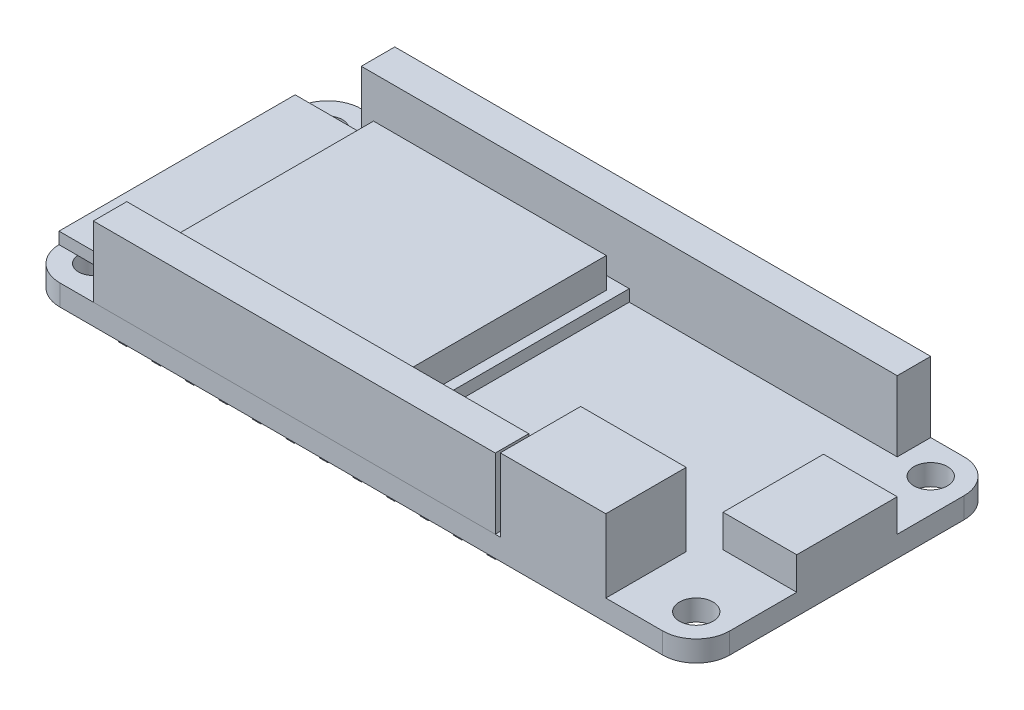
SolidWorks part; units mm, degrees
ref_plane "Front Plane" through (0, 0, 0) normal (0, 0, 1) x (1, 0, 0)
ref_plane "Top Plane" through (0, 0, 0) normal (0, 1, 0) x (1, 0, 0)
ref_plane "Right Plane" through (0, 0, 0) normal (1, 0, 0) x (0, 0, -1)
sketch "Sketch1" plane through (0, 0, 0) normal (0, 1, 0) x (1, 0, 0)
  line L0 (6.35, 1.27) -> (8.89, 1.27) construction
  line L1 (2.54, 0) -> (48.26, 0)
  line L2 (0, 2.54) -> (0, 20.32)
  line L3 (2.54, 22.86) -> (48.26, 22.86)
  line L4 (50.8, 2.54) -> (50.8, 20.32)
  arc A0 (0, 20.32) -> (2.54, 22.86) centre (2.54, 20.32) cw
  arc A1 (2.54, 0) -> (0, 2.54) centre (2.54, 2.54) cw
  arc A2 (48.26, 0) -> (50.8, 2.54) centre (48.26, 2.54) ccw
  arc A3 (48.26, 22.86) -> (50.8, 20.32) centre (48.26, 20.32) cw
  circle A4 centre (48.26, 20.32) radius 1.27
  circle A5 centre (48.26, 2.54) radius 1.27
  circle A6 centre (6.35, 21.59) radius 0.508
  circle A7 centre (8.89, 21.59) radius 0.508
  circle A8 centre (11.43, 21.59) radius 0.508
  circle A9 centre (13.97, 21.59) radius 0.508
  circle A10 centre (16.51, 21.59) radius 0.508
  circle A11 centre (19.05, 21.59) radius 0.508
  circle A12 centre (21.59, 21.59) radius 0.508
  circle A13 centre (24.13, 21.59) radius 0.508
  circle A14 centre (26.67, 21.59) radius 0.508
  circle A15 centre (29.21, 21.59) radius 0.508
  circle A16 centre (31.75, 21.59) radius 0.508
  circle A17 centre (34.29, 21.59) radius 0.508
  circle A18 centre (36.83, 21.59) radius 0.508
  circle A19 centre (39.37, 21.59) radius 0.508
  circle A20 centre (41.91, 21.59) radius 0.508
  circle A21 centre (44.45, 21.59) radius 0.508
  circle A22 centre (2.54, 20.32) radius 1.1176
  circle A23 centre (2.54, 2.54) radius 1.1176
  circle A24 centre (6.35, 1.27) radius 0.508
  circle A25 centre (8.89, 1.27) radius 0.508
  circle A26 centre (11.43, 1.27) radius 0.508
  circle A27 centre (13.97, 1.27) radius 0.508
  circle A28 centre (16.51, 1.27) radius 0.508
  circle A29 centre (19.05, 1.27) radius 0.508
  circle A30 centre (21.59, 1.27) radius 0.508
  circle A31 centre (24.13, 1.27) radius 0.508
  circle A32 centre (26.67, 1.27) radius 0.508
  circle A33 centre (29.21, 1.27) radius 0.508
  circle A34 centre (31.75, 1.27) radius 0.508
  circle A35 centre (34.29, 1.27) radius 0.508
  point P7 (0, 22.86)
  point P10 (0, 0)
  point P13 (50.8, 0)
  dimension "D3" = 2.54
  dimension "D4" = 2.54
  dimension "D5" = 1.27
  dimension "D6" = 1.016
  dimension "D10" = 2.2352
  dimension "D11" = 1.27
  dimension "D1" = 50.8
  dimension "D2" = 22.86
  dimension "D7" = 6.35
  dimension "D9" = 2.54
  dimension "D13" = 2.54
  dimension "D8" = 16
  dimension "D12" = 12
extrude "Boss-Extrude1" add sketch "Sketch1" along normal blind 1.5875 contours A23 | A22 | A4 | A5 | L2 A0 L3 A3 L4 A2 L1 A1 region at (48.26, 0, -20.32) region at (48.26, 0, -2.54) region at (2.54, 0, -20.32) region at (2.54, 0, -2.54)
sketch "Sketch2" plane through (0, 1.5875, 1.5875) normal (0, 1, 0) x (1, 0, 0)
  line L0 (0, 13.0175) -> (50.8, 13.0175) construction
  line L4 (50.8, 4.1275) -> (50.8, 21.9075) construction
  line L5 (0, 4.1275) -> (0, 21.9075) construction
  line L6 (0, 4.064) -> (25.4, 4.064)
  line L7 (0, 4.064) -> (0, 21.971)
  line L8 (0, 21.971) -> (25.4, 21.971)
  line L9 (25.4, 4.064) -> (25.4, 21.971)
  line L10 (24.638, 20.9296) -> (6.985, 20.9296)
  line L11 (24.638, 20.9296) -> (24.638, 5.1054)
  line L12 (24.638, 5.1054) -> (6.985, 5.1054)
  line L13 (6.985, 20.9296) -> (6.985, 5.1054)
  line L14 (35.941, 7.6835) -> (43.942, 7.6835)
  line L15 (35.941, 7.6835) -> (35.941, 1.5875)
  line L16 (35.941, 1.5875) -> (43.942, 1.5875)
  line L17 (43.942, 7.6835) -> (43.942, 1.5875)
  line L18 (45.212, 16.8275) -> (50.8, 16.8275)
  line L19 (45.212, 16.8275) -> (45.212, 9.2075)
  line L20 (45.212, 9.2075) -> (50.8, 9.2075)
  line L21 (50.8, 16.8275) -> (50.8, 9.2075)
  line L22 (2.54, 1.5875) -> (48.26, 1.5875) construction
  point P10 (0, 13.0175)
  point P95 (6.985, 13.0175)
  point P96 (25.4, 13.0175)
  point P97 (45.212, 13.0175)
  dimension "D3" = 6.985
  dimension "D4" = 6.858
  dimension "D14" = 17.907
  dimension "D15" = 15.8242
  dimension "D16" = 7.62
  dimension "D17" = 6.096
  dimension "D19" = 17.653
  dimension "D20" = 25.4
  dimension "D22" = 8.001
  dimension "D23" = 5.588
extrude "Boss-Extrude2" add sketch "Sketch2" along normal blind 0.889 contours L7 L8 L9 L6
extrude "Boss-Extrude3" add sketch "Sketch2<3>" along normal blind 2.286 from surface contours L13 L12 L11 L10 starting at face at (12.7, 2.4765, -11.43)
sketch "Sketch2<3>" plane through (0, 1.5875, 1.5875) normal (0, 1, 0) x (1, 0, 0) same geometry as "Sketch2"
extrude "Boss-Extrude4" add sketch "Sketch2<4>" along normal blind 5.5372 contours L16 L17 L14 L15
sketch "Sketch2<4>" plane through (0, 1.5875, 1.5875) normal (0, 1, 0) x (1, 0, 0) same geometry as "Sketch2"
extrude "Boss-Extrude5" add sketch "Sketch2<5>" along normal blind 2.4638 contours L20 L21 L18 L19
sketch "Sketch2<5>" plane through (0, 1.5875, 1.5875) normal (0, 1, 0) x (1, 0, 0) same geometry as "Sketch2"
sketch "Sketch3" plane through (0, 0, 0) normal (0, -1, 0) x (1, 0, 0)
  line L0 (8.5725, -21.9075) -> (9.2075, -21.9075)
  line L1 (6.0325, -21.9075) -> (6.6675, -21.9075)
  line L2 (6.0325, -21.9075) -> (6.0325, -21.2725)
  line L3 (6.0325, -21.2725) -> (6.6675, -21.2725)
  line L4 (6.6675, -21.9075) -> (6.6675, -21.2725)
  line L5 (6.0325, -21.9075) -> (6.6675, -21.2725) construction
  line L6 (6.0325, -21.2725) -> (6.6675, -21.9075) construction
  line L7 (9.2075, -21.9075) -> (9.2075, -21.2725)
  line L8 (8.5725, -21.2725) -> (9.2075, -21.2725)
  line L9 (8.5725, -21.9075) -> (8.5725, -21.2725)
  line L10 (11.1125, -21.9075) -> (11.7475, -21.9075)
  line L11 (11.7475, -21.9075) -> (11.7475, -21.2725)
  line L12 (11.1125, -21.2725) -> (11.7475, -21.2725)
  line L13 (11.1125, -21.9075) -> (11.1125, -21.2725)
  line L14 (13.6525, -21.9075) -> (14.2875, -21.9075)
  line L15 (14.2875, -21.9075) -> (14.2875, -21.2725)
  line L16 (13.6525, -21.2725) -> (14.2875, -21.2725)
  line L17 (13.6525, -21.9075) -> (13.6525, -21.2725)
  line L18 (16.1925, -21.9075) -> (16.8275, -21.9075)
  line L19 (16.8275, -21.9075) -> (16.8275, -21.2725)
  line L20 (16.1925, -21.2725) -> (16.8275, -21.2725)
  line L21 (16.1925, -21.9075) -> (16.1925, -21.2725)
  line L22 (18.7325, -21.9075) -> (19.3675, -21.9075)
  line L23 (19.3675, -21.9075) -> (19.3675, -21.2725)
  line L24 (18.7325, -21.2725) -> (19.3675, -21.2725)
  line L25 (18.7325, -21.9075) -> (18.7325, -21.2725)
  line L26 (21.2725, -21.9075) -> (21.9075, -21.9075)
  line L27 (21.9075, -21.9075) -> (21.9075, -21.2725)
  line L28 (21.2725, -21.2725) -> (21.9075, -21.2725)
  line L29 (21.2725, -21.9075) -> (21.2725, -21.2725)
  line L30 (23.8125, -21.9075) -> (24.4475, -21.9075)
  line L31 (24.4475, -21.9075) -> (24.4475, -21.2725)
  line L32 (23.8125, -21.2725) -> (24.4475, -21.2725)
  line L33 (23.8125, -21.9075) -> (23.8125, -21.2725)
  line L34 (26.3525, -21.9075) -> (26.9875, -21.9075)
  line L35 (26.9875, -21.9075) -> (26.9875, -21.2725)
  line L36 (26.3525, -21.2725) -> (26.9875, -21.2725)
  line L37 (26.3525, -21.9075) -> (26.3525, -21.2725)
  line L38 (28.8925, -21.9075) -> (29.5275, -21.9075)
  line L39 (29.5275, -21.9075) -> (29.5275, -21.2725)
  line L40 (28.8925, -21.2725) -> (29.5275, -21.2725)
  line L41 (28.8925, -21.9075) -> (28.8925, -21.2725)
  line L42 (31.4325, -21.9075) -> (32.0675, -21.9075)
  line L43 (32.0675, -21.9075) -> (32.0675, -21.2725)
  line L44 (31.4325, -21.2725) -> (32.0675, -21.2725)
  line L45 (31.4325, -21.9075) -> (31.4325, -21.2725)
  line L46 (33.9725, -21.9075) -> (34.6075, -21.9075)
  line L47 (34.6075, -21.9075) -> (34.6075, -21.2725)
  line L48 (33.9725, -21.2725) -> (34.6075, -21.2725)
  line L49 (33.9725, -21.9075) -> (33.9725, -21.2725)
  line L50 (36.5125, -21.9075) -> (37.1475, -21.9075)
  line L51 (37.1475, -21.9075) -> (37.1475, -21.2725)
  line L52 (36.5125, -21.2725) -> (37.1475, -21.2725)
  line L53 (36.5125, -21.9075) -> (36.5125, -21.2725)
  line L54 (39.0525, -21.9075) -> (39.6875, -21.9075)
  line L55 (39.6875, -21.9075) -> (39.6875, -21.2725)
  line L56 (39.0525, -21.2725) -> (39.6875, -21.2725)
  line L57 (39.0525, -21.9075) -> (39.0525, -21.2725)
  line L58 (41.5925, -21.9075) -> (42.2275, -21.9075)
  line L59 (42.2275, -21.9075) -> (42.2275, -21.2725)
  line L60 (41.5925, -21.2725) -> (42.2275, -21.2725)
  line L61 (41.5925, -21.9075) -> (41.5925, -21.2725)
  line L62 (44.1325, -21.9075) -> (44.7675, -21.9075)
  line L63 (44.7675, -21.9075) -> (44.7675, -21.2725)
  line L64 (44.1325, -21.2725) -> (44.7675, -21.2725)
  line L65 (44.1325, -21.9075) -> (44.1325, -21.2725)
  line L66 (6.0325, -21.9075) -> (8.5725, -21.9075) construction
  line L67 (8.5725, -0.9525) -> (8.5725, -1.5875)
  line L68 (6.0325, -0.9525) -> (6.6675, -0.9525)
  line L69 (6.0325, -0.9525) -> (6.0325, -1.5875)
  line L70 (6.0325, -1.5875) -> (6.6675, -1.5875)
  line L71 (6.6675, -0.9525) -> (6.6675, -1.5875)
  line L72 (6.0325, -0.9525) -> (6.6675, -1.5875) construction
  line L73 (6.0325, -1.5875) -> (6.6675, -0.9525) construction
  line L74 (8.5725, -1.5875) -> (9.2075, -1.5875)
  line L75 (9.2075, -0.9525) -> (9.2075, -1.5875)
  line L76 (8.5725, -0.9525) -> (9.2075, -0.9525)
  line L77 (11.1125, -0.9525) -> (11.1125, -1.5875)
  line L78 (11.1125, -1.5875) -> (11.7475, -1.5875)
  line L79 (11.7475, -0.9525) -> (11.7475, -1.5875)
  line L80 (11.1125, -0.9525) -> (11.7475, -0.9525)
  line L81 (13.6525, -0.9525) -> (13.6525, -1.5875)
  line L82 (13.6525, -1.5875) -> (14.2875, -1.5875)
  line L83 (14.2875, -0.9525) -> (14.2875, -1.5875)
  line L84 (13.6525, -0.9525) -> (14.2875, -0.9525)
  line L85 (16.1925, -0.9525) -> (16.1925, -1.5875)
  line L86 (16.1925, -1.5875) -> (16.8275, -1.5875)
  line L87 (16.8275, -0.9525) -> (16.8275, -1.5875)
  line L88 (16.1925, -0.9525) -> (16.8275, -0.9525)
  line L89 (18.7325, -0.9525) -> (18.7325, -1.5875)
  line L90 (18.7325, -1.5875) -> (19.3675, -1.5875)
  line L91 (19.3675, -0.9525) -> (19.3675, -1.5875)
  line L92 (18.7325, -0.9525) -> (19.3675, -0.9525)
  line L93 (21.2725, -0.9525) -> (21.2725, -1.5875)
  line L94 (21.2725, -1.5875) -> (21.9075, -1.5875)
  line L95 (21.9075, -0.9525) -> (21.9075, -1.5875)
  line L96 (21.2725, -0.9525) -> (21.9075, -0.9525)
  line L97 (23.8125, -0.9525) -> (23.8125, -1.5875)
  line L98 (23.8125, -1.5875) -> (24.4475, -1.5875)
  line L99 (24.4475, -0.9525) -> (24.4475, -1.5875)
  line L100 (23.8125, -0.9525) -> (24.4475, -0.9525)
  line L101 (26.3525, -0.9525) -> (26.3525, -1.5875)
  line L102 (26.3525, -1.5875) -> (26.9875, -1.5875)
  line L103 (26.9875, -0.9525) -> (26.9875, -1.5875)
  line L104 (26.3525, -0.9525) -> (26.9875, -0.9525)
  line L105 (28.8925, -0.9525) -> (28.8925, -1.5875)
  line L106 (28.8925, -1.5875) -> (29.5275, -1.5875)
  line L107 (29.5275, -0.9525) -> (29.5275, -1.5875)
  line L108 (28.8925, -0.9525) -> (29.5275, -0.9525)
  line L109 (31.4325, -0.9525) -> (31.4325, -1.5875)
  line L110 (31.4325, -1.5875) -> (32.0675, -1.5875)
  line L111 (32.0675, -0.9525) -> (32.0675, -1.5875)
  line L112 (31.4325, -0.9525) -> (32.0675, -0.9525)
  line L113 (33.9725, -0.9525) -> (33.9725, -1.5875)
  line L114 (33.9725, -1.5875) -> (34.6075, -1.5875)
  line L115 (34.6075, -0.9525) -> (34.6075, -1.5875)
  line L116 (33.9725, -0.9525) -> (34.6075, -0.9525)
  line L117 (6.0325, -0.9525) -> (8.5725, -0.9525) construction
  point P0 (6.35, -21.59)
  point P5 (6.35, -1.27)
  dimension "D1" = 0.635
  dimension "D2" = 16
  dimension "D3" = 2.54
  dimension "D4" = 0.635
  dimension "D5" = 12
  dimension "D6" = 2.54
extrude "Boss-Extrude6" add sketch "Sketch3" along normal blind 1.016 separate body
sketch "Sketch4" plane through (0, 1.5875, 0) normal (0, 1, 0) x (1, 0, 0)
  line L0 (2.54, 22.86) -> (48.26, 22.86) construction
  line L1 (5.08, 2.54) -> (35.56, 2.54)
  line L2 (5.08, 2.54) -> (5.08, 0)
  line L3 (5.08, 0) -> (35.56, 0)
  line L4 (35.56, 2.54) -> (35.56, 0)
  line L5 (5.08, 20.32) -> (45.72, 20.32)
  line L6 (5.08, 20.32) -> (5.08, 22.86)
  line L7 (5.08, 22.86) -> (45.72, 22.86)
  line L8 (45.72, 20.32) -> (45.72, 22.86)
  line L9 (2.54, 0) -> (48.26, 0) construction
  dimension "D1" = 2.54
  dimension "D2" = 40.64
  dimension "D3" = 1.27
  dimension "D4" = 30.48
extrude "Boss-Extrude7" add sketch "Sketch4" along normal blind 5.334 separate body
